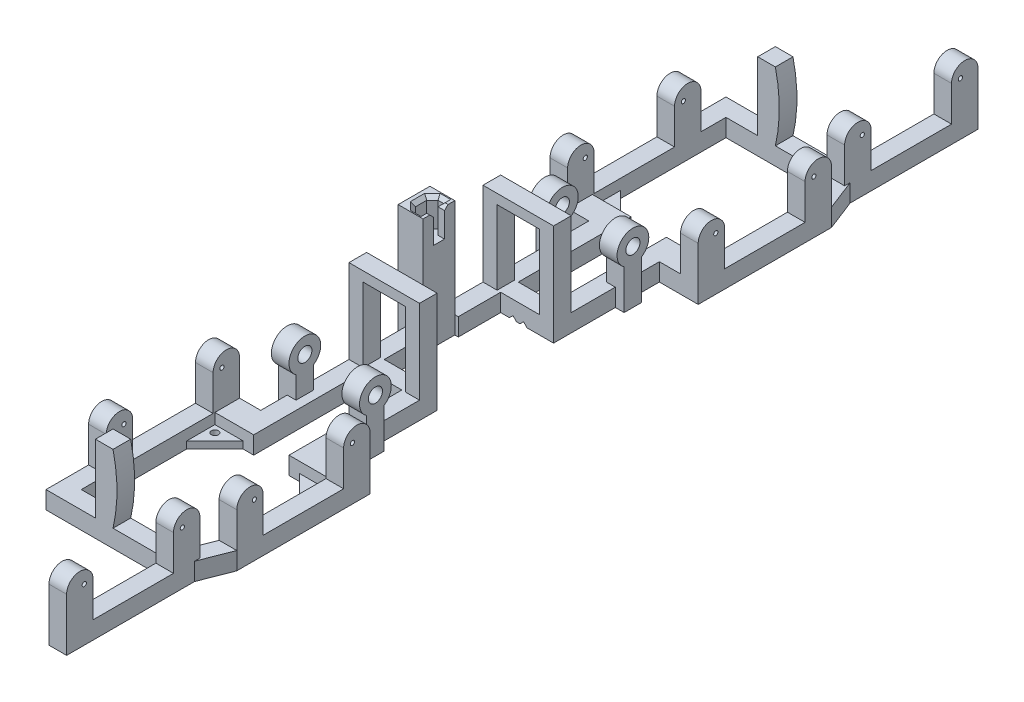
SolidWorks part; units mm, degrees
ref_plane "Спереди" through (0, 0, 0) normal (0, 0, 1) x (1, 0, 0)
ref_plane "Сверху" through (0, 0, 0) normal (0, 1, 0) x (1, 0, 0)
ref_plane "Справа" through (0, 0, 0) normal (1, 0, 0) x (0, 0, -1)
sketch "Эскиз2" plane through (0, 0, 0) normal (0, 0, 1) x (1, 0, 0)
  line L0 (1.5, 32) -> (1.5, 31) construction
  line L1 (0, 0) -> (0.5, 0)
  line L2 (0, 0) -> (0, 5)
  line L3 (0, 32) -> (10, 32)
  line L4 (10, 0) -> (10, 32)
  line L5 (10, 0) -> (5, 0)
  line L6 (10, 0) -> (10, 5)
  line L7 (10, 5) -> (5, 5)
  line L8 (5, 0) -> (5, 5)
  line L9 (6, 5) -> (0, 5)
  line L10 (6, 5) -> (6, 26)
  line L11 (6, 26) -> (0, 26)
  line L12 (1.5, 1) -> (2.5, 0)
  line L13 (1.5, 31) -> (2.5, 32)
  line L14 (1.5, 31) -> (0.5, 32)
  line L15 (10, 16) -> (6, 16) construction
  line L16 (0, 26) -> (0, 32)
  line L17 (1.5, 1) -> (0.5, 0)
  line L18 (2.5, 0) -> (10, 0)
  dimension "D1" = 10
  dimension "D2" = 32
  dimension "D3" = 5
  dimension "D4" = 5
  dimension "D5" = 21
  dimension "D6" = 6
  dimension "D7" = 1.5
  dimension "D8" = 1
extrude "Rail1" add sketch "Эскиз2<5>" against normal blind 27.5 contours L6 L7 L8 L5
sketch "Эскиз2<5>" plane through (0, 0, 0) normal (0, 0, 1) x (1, 0, 0) same geometry as "Эскиз2"
extrude "ArchForThread1" add sketch "Эскиз2" along normal mid plane 5 contours L16 L11 L10 L7 L4 L3 L13 L14 | L12 L18 L8 L9 L2 L1 L17 region at (2.5417, 2.5903, 0) region at (6.7867, 21.0513, 0)
mirror "Зеркальное отражение2" about plane through (0, 0, 0) normal (1, 0, 0) of "ArchForThread1"
mirror "Зеркальное отражение3" about plane through (0, 0, 0) normal (1, 0, 0) of "Rail1"
extrude "Rail2" add sketch "Эскиз2<6>" along normal blind 2.5 contours L8 L5 L4 L7 region at (7.5, 2.5, 0)
sketch "Эскиз2<6>" plane through (0, 0, 0) normal (0, 0, 1) x (1, 0, 0) same geometry as "Эскиз2"
sketch "Эскиз3" plane through (0, 0, 0) normal (0, 0, 1) x (1, 0, 0)
  line L1 (-5, 0) -> (-10, 0)
  line L2 (-5, 0) -> (-5, 5)
  line L3 (-5, 5) -> (-10, 5)
  line L4 (-10, 0) -> (-10, 5)
extrude "CellNest" add sketch "Эскиз3" along normal blind 14.5
sketch "Эскиз4" plane through (0, 0, 0) normal (0, 1, 0) x (1, 0, 0)
  line L0 (-5, -19) -> (-6, -19) construction
  line L1 (-6, -14.5) -> (-13.05, -14.5)
  line L2 (-5, -19) -> (-5, -14.5) construction
  line L3 (-6, -23.5) -> (-13.05, -23.5)
  line L4 (-13.05, -14.5) -> (-13.05, -23.5)
  line L5 (-6, -14.5) -> (-6, -23.5)
  line L6 (-5, -23.5) -> (-5, -19) construction
  line L7 (-5, -14.5) -> (-6, -14.5) construction
  line L8 (-5, -23.5) -> (-6, -23.5) construction
  dimension "D1" = 9
  dimension "D2" = 8.05
  dimension "D3" = 1
extrude "Бобышка-Вытянуть6" add sketch "Эскиз4" along normal blind 25
sketch "Эскиз5" plane through (0, 25, 0) normal (0, 1, 0) x (1, 0, 0)
  line L0 (-13.05, -19) -> (-11.05, -19) construction
  line L1 (-13.05, -23.5) -> (-6, -23.5)
  line L2 (-13.05, -23.5) -> (-13.05, -14.5)
  line L3 (-13.05, -14.5) -> (-6, -14.5)
  line L4 (-6, -23.5) -> (-6, -20.6)
  line L5 (-11.05, -17.4) -> (-11.05, -20.6)
  line L6 (-11.05, -20.6) -> (-9.45, -22.2)
  line L7 (-9.45, -22.2) -> (-7.85, -22.2)
  line L8 (-7.85, -22.2) -> (-7.85, -20.6)
  line L9 (-7.85, -20.6) -> (-6, -20.6)
  line L10 (-7.85, -17.4) -> (-6, -17.4)
  line L11 (-7.85, -15.8) -> (-7.85, -17.4)
  line L12 (-9.45, -15.8) -> (-7.85, -15.8)
  line L13 (-11.05, -17.4) -> (-9.45, -15.8)
  line L14 (-6, -14.5) -> (-6, -17.4)
  dimension "D1" = 2
  dimension "D2" = 1.6
  dimension "D3" = 1.85
  dimension "D4" = 1.6
  dimension "D5" = 1.6
  dimension "D6" = 2.9
  dimension "D7" = 7.05
extrude "Бобышка-Вытянуть7" add sketch "Эскиз5" along normal blind 8
chamfer "Фаска1" distance 1 angle 45 9 edges at (-6.925, 33, 20.6) (-7.85, 33, 21.4) (-8.65, 33, 22.2) (-10.25, 33, 21.4) (-6.925, 33, 17.4) (-7.85, 33, 16.6) (-8.65, 33, 15.8) (-10.25, 33, 16.6) (-11.05, 33, 19)
sketch "Эскиз6" plane through (0, 0, 0) normal (0, 1, 0) x (1, 0, 0)
  line L0 (-10, 0) -> (10, 0) construction
  line L1 (-10, -2.5) -> (-10, 2.5) construction
  line L2 (10, -2.5) -> (10, 2.5) construction
sketch "Эскиз7" plane through (10, 0, 0) normal (1, 0, 0) x (0, 0, -1)
  line L0 (0, 0) -> (17.5, 0) construction
  line L1 (27.5, 0) -> (-2.5, 0) construction
  line L2 (17.5, 0) -> (17.5, 15) construction
  line L3 (20, 11.2583) -> (20, 0)
  line L4 (20, 0) -> (15, 0)
  line L5 (15, 11.2583) -> (15, 0)
  circle A0 centre (17.5, 15) radius 2
  arc A1 (20, 11.2583) -> (15, 11.2583) centre (17.5, 15) ccw
  dimension "D3" = 9
  dimension "D4" = 4
  dimension "D1" = 17.5
  dimension "D2" = 15
  dimension "D5" = 2.5
extrude "Бобышка-Вытянуть8" add sketch "Эскиз7" along normal mid plane 5
mirror "Зеркальное отражение4" about plane through (0, 0, 0) normal (1, 0, 0) of "Бобышка-Вытянуть8"
sketch "Эскиз12" plane through (0, 0, 0) normal (0, 1, 0) x (1, 0, 0)
  line L1 (5, 27.5) -> (21, 27.5)
  line L2 (5, 27.5) -> (5, 34.5)
  line L3 (5, 34.5) -> (21, 34.5)
  line L4 (21, 27.5) -> (21, 34.5)
  dimension "D1" = 7
  dimension "D2" = 16
extrude "Бобышка-Вытянуть9" add sketch "Эскиз12" along normal blind 5
sketch "Эскиз13" plane through (21, 0, 0) normal (1, 0, 0) x (0, 0, -1)
  line L0 (27.5, 15) -> (35, 15) construction
  line L1 (27.5, 0) -> (65.3, 0)
  line L2 (27.5, 0) -> (27.5, 15)
  line L3 (35, 15) -> (35, 5) construction
  line L4 (65.3, 0) -> (65.3, 15)
  line L5 (27.5, 5) -> (34.5, 5) construction
  line L6 (31.25, 18.5) -> (31.25, 15) construction
  line L7 (35, 15) -> (35, 5)
  line L8 (46.4, 0) -> (46.4, 5) construction
  line L9 (57.8, 15) -> (57.8, 5)
  line L10 (65.3, 0) -> (65.3, 15)
  line L11 (35, 5) -> (57.8, 5)
  line L12 (31.25, 15) -> (32.5, 15) construction
  arc A0 (35, 15) -> (27.5, 15) centre (31.25, 15) ccw
  circle A1 centre (32.5, 15) radius 0.6
  circle A2 centre (60.3, 15) radius 0.6
  arc A3 (57.8, 15) -> (65.3, 15) centre (61.55, 15) cw
  line M1 (27.5, 0) -> (34.5, 0)
  line M2 (34.5, 0) -> (34.5, 5)
  line M3 (34.5, 5) -> (27.5, 5)
  line M4 (27.5, 5) -> (27.5, 0)
  dimension "D5" = 5
  dimension "D6" = 1.2
  dimension "D1" = 15
  dimension "D2" = 37.8
  dimension "D3" = 7.5
  dimension "D4" = 3.5
extrude "Бобышка-Вытянуть10" add sketch "Эскиз13" against normal blind 5 contours A3 L9 L11 L1 L4 M2 | M4 M1 M2 M3 | L7 A0 L2 M3 region at (21, 2.5, -31) region at (21, 2.5, -34.9219)
mirror "Зеркальное отражение5" about plane through (0, 0, 0) normal (1, 0, 0) of "Бобышка-Вытянуть9", "Бобышка-Вытянуть10"
sketch "Эскиз14" plane through (0, 0, 0) normal (0, 1, 0) x (1, 0, 0)
  line L0 (21, 65.3) -> (21, 74.3) construction
  line L1 (21, 74.3) -> (17.5, 74.3) construction
  line L2 (21, 65.3) -> (17.5, 74.3)
  line L3 (21, 65.3) -> (16, 65.3)
  line L4 (17.5, 74.3) -> (12.5, 74.3)
  line L5 (16, 65.3) -> (12.5, 74.3)
  line L6 (21, 27.5) -> (17.5, 74.3) construction
  dimension "D1" = 3.5
  dimension "D2" = 9
  dimension "D3" = 5
  dimension "D4" = 46.9307
extrude "Бобышка-Вытянуть11" add sketch "Эскиз14" along normal blind 5
pattern_linear "Линейный массив1" count 2 spacing 45 along (-0.0746, 0, -0.9972) of "Бобышка-Вытянуть10"
sketch "Эскиз15" plane through (0, 0, 0) normal (0, 1, 0) x (1, 0, 0)
  line L0 (-16, 72.3747) -> (-21.0002, 72.3747) construction
  line L1 (13.2487, 72.3747) -> (-16, 72.3747)
  line L2 (13.2487, 72.3747) -> (13.2487, 77.3747)
  line L3 (13.2487, 77.3747) -> (-21.0002, 77.3747)
  line L4 (-21.0002, 72.3747) -> (-21.0002, 77.3747)
  line L6 (-21.0002, 72.3747) -> (-21.0002, 65.3)
  line L7 (-21.0002, 65.3) -> (-16, 65.3)
  line L8 (-16, 72.3747) -> (-16, 65.3)
  dimension "D1" = 5
extrude "Бобышка-Вытянуть12" add sketch "Эскиз15" along normal blind 5
sketch "Эскиз16" plane through (0, 0, -77.3747) normal (0, 0, -1) x (-1, 0, 0)
  line L0 (7.0002, 5) -> (21.0002, 5) construction
  line L1 (-12.644, 5) -> (21.0002, 5) construction
  line L2 (2.0002, 5) -> (7.0002, 5)
  line L3 (2.0002, 5) -> (2.0002, 24.3705)
  line L4 (2.0002, 24.3705) -> (7.0002, 24.3705)
  line L7 (7.0002, 5) -> (7.0002, 24.3705)
  arc A0 (2.0002, 5) -> (2.0002, 24.3705) centre (43.3569, 14.6852) cw
  line M1 (21.0002, 5) -> (-12.644, 5)
  dimension "D1" = 5
  dimension "D2" = 14
extrude "Бобышка-Вытянуть13" add sketch "Эскиз16" against normal blind 5 contours A0 L3 | L7 L4 L3 M1 region at (-4.5002, 14.6852, -77.3747) region at (-1.5521, 14.6852, -77.3747)
sketch "Эскиз17" plane through (0, 33, 0) normal (0, 1, 0) x (1, 0, 0)
  line L0 (-13.05, -14.5) -> (-13.05, -23.5) construction
  point P0 (-13.05, -19)
ref_plane "Плоскость1" through (0, 0, 19) normal (0, 0, 1) x (1, 0, 0)
mirror "Зеркальное отражение8" about plane through (0, 0, 19) normal (0, 0, 1) of "CellNest"
mirror "Зеркальное отражение13" about plane through (0, 0, 19) normal (0, 0, 1) of "Зеркальное отражение2"
mirror "Зеркальное отражение19" about plane through (0, 0, 19) normal (0, 0, 1) of "Rail1"
mirror "Зеркальное отражение20" about plane through (0, 0, 19) normal (0, 0, 1) of "Rail2"
mirror "Зеркальное отражение21" about plane through (0, 0, 0) normal (1, 0, 0) of "Зеркальное отражение19", "Зеркальное отражение20"
mirror "Зеркальное отражение22" about plane through (0, 0, 19) normal (0, 0, 1) of "Зеркальное отражение4"
mirror "Зеркальное отражение23" about plane through (0, 0, 19) normal (0, 0, 1) of "Зеркальное отражение5"
mirror "Зеркальное отражение24" about plane through (0, 0, 19) normal (0, 0, 1) of "Бобышка-Вытянуть11"
mirror "Зеркальное отражение25" about plane through (0, 0, 19) normal (0, 0, 1) of "Линейный массив1"
mirror "Зеркальное отражение26" about plane through (0, 0, 19) normal (0, 0, 1) of "Бобышка-Вытянуть13", "Бобышка-Вытянуть12"
sketch "Эскиз18" plane through (0, 0, 0) normal (0, 1, 0) x (1, 0, 0)
  line L0 (16, 34.5) -> (8, 34.5)
  line L1 (16, 34.5) -> (5, 34.5) construction
  line L2 (8, 34.5) -> (16, 42.5)
  line L3 (16, 35) -> (16, 57.8) construction
  line L4 (16, 42.5) -> (16, 34.5)
  line L5 (12, 38.5) -> (16, 34.5) construction
  circle A0 centre (14, 36.5) radius 1
  dimension "D3" = 2
  dimension "D1" = 8
  dimension "D2" = 8
extrude "Бобышка-Вытянуть14" add sketch "Эскиз18" along normal blind 2
mirror "ЗеркОтр_ЯзычкиКрепКОснов" about plane through (0, 0, 0) normal (1, 0, 0) of "Бобышка-Вытянуть14"
mirror "ЗеркОтр_ЯзычкиКрепКОснов2" about plane through (0, 0, 19) normal (0, 0, 1) of "ЗеркОтр_ЯзычкиКрепКОснов"
sketch "Sketch1" plane through (0, 0, -2.5) normal (0, 0, -1) x (-1, 0, 0)
  line L0 (-10, 28.7758) -> (10, 28.7758)
  line L1 (-10, 5) -> (-10, 32) construction
  line L2 (10, 5) -> (10, 32) construction
  line L3 (10, 28.7758) -> (10, 34.6129)
  line L4 (10, 34.6129) -> (-10, 34.6129)
  line L5 (-10, 34.6129) -> (-10, 28.7758)
extrude "Cut-Extrude1" cut sketch "Sketch1" against normal blind 10
mirror "Mirror1" about plane through (0, 0, 19) normal (0, 0, 1) of "Cut-Extrude1"
